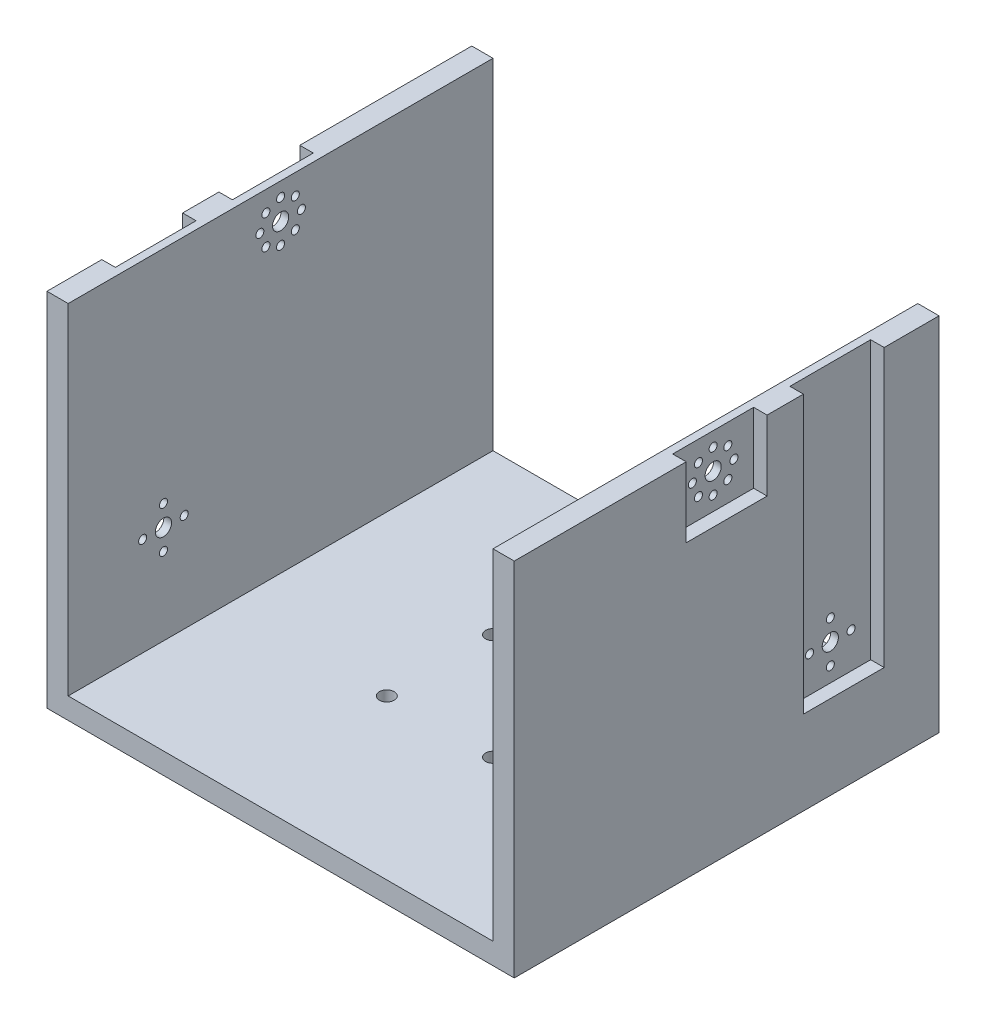
SolidWorks part; units mm, degrees
ref_plane "Front" through (0, 0, 0) normal (0, 0, 1) x (1, 0, 0)
ref_plane "Top" through (0, 0, 0) normal (0, 1, 0) x (1, 0, 0)
ref_plane "Right" through (0, 0, 0) normal (1, 0, 0) x (0, 0, -1)
sketch "Sketch2" plane through (0, 0, 0) normal (0, 1, 0) x (1, 0, 0)
  line L0 (0, 0) -> (0, -100) construction
  line L1 (-100, -100) -> (100, -100)
  line L2 (-100, -100) -> (-100, 100)
  line L3 (-100, 100) -> (100, 100)
  line L4 (100, -100) -> (100, 100)
  line L5 (0, 0) -> (-100, 0) construction
  point P0 (0, 0)
  dimension "D1" = 200
  dimension "D2" = 200
extrude "Boss-Extrude1" add sketch "Sketch2" along normal blind 10
sketch "Sketch3" plane through (0, 0, 0) normal (0, 1, 0) x (1, 0, 0)
  line L0 (-100, -100) -> (100, -100) construction
  line L1 (-100, 100) -> (-110, 100)
  line L2 (-100, 100) -> (-100, -100)
  line L3 (-100, -100) -> (-110, -100)
  line L4 (-110, 100) -> (-110, -100)
  line L5 (0, 0) -> (0, 100) construction
  line L6 (100, 100) -> (-100, 100) construction
  line L7 (110, 100) -> (110, -100)
  line L8 (100, -100) -> (110, -100)
  line L9 (100, 100) -> (100, -100)
  line L10 (100, 100) -> (110, 100)
  dimension "D1" = 10
extrude "Boss-Extrude2" add sketch "Sketch3" along normal blind 170
sketch "Sketch4" plane through (0, 10, 0) normal (0, 1, 0) x (1, 0, 0)
  point P4 (0, 0)
hole_wizard "M6 Clearance Hole1" positions "Sketch5" profile "Sketch6" hole size "M6" standard "ANSI Metric" end condition up to next
sketch "Sketch5" plane through (0, 10, 0) normal (0, 1, 0) x (1, 0, 0)
  line L0 (0, 0) -> (0, 25) construction
  line L1 (0, 25) -> (-25, 25) construction
  line L3 (0, 25) -> (25, 25) construction
  point P0 (-25, 25)
  point P13 (25, 25)
  point P14 (25, -25)
  point P15 (-25, -25)
  dimension "D1" = 25
  dimension "D2" = 4
sketch "Sketch6" plane through (-25, 10, -25) normal (1, 0, 0) x (0, 0, 1)
  line L0 (0, 0) -> (0, 10)
  line L1 (0, 10) -> (3.5, 10)
  line L2 (3.5, 10) -> (3.5, 0)
  line L5 (3.5, 0) -> (0, 0)
  line L11 (0, -6.35) -> (0, 107.95) construction
  dimension "Thru Hole Dia." = 7
  dimension "Thru Hole Depth" = 10
sketch "Sketch7" plane through (100, 0, 0) normal (-1, 0, 0) x (0, 0, 1)
  line L0 (-100, 170) -> (100, 170) construction
  line L1 (0, 153.49) -> (0, 163.269) construction
  line L2 (0, 153.49) -> (0, 163.269) construction
  circle A0 centre (0, 153.49) radius 3.81
  circle A1 centre (0, 163.269) radius 1.8987
  circle A2 centre (6.9148, 160.4048) radius 1.8987
  circle A3 centre (9.779, 153.49) radius 1.8987
  circle A4 centre (6.9148, 146.5752) radius 1.8987
  circle A5 centre (0, 143.711) radius 1.8987
  circle A6 centre (-6.9148, 146.5752) radius 1.8987
  circle A7 centre (-9.779, 153.49) radius 1.8987
  circle A8 centre (-6.9148, 160.4048) radius 1.8987
  point P7 (0, 170)
  dimension "D1" = 7.62
  dimension "D3" = 3.7973
  dimension "D2" = 16.51
  dimension "D6" = 9.779
  dimension "D5" = 8
extrude "Cut-Extrude1" cut sketch "Sketch7" against normal through all both and the other way through all
sketch "Sketch8" plane through (0, 170, 0) normal (0, 1, 0) x (1, 0, 0)
  line L1 (103.65, -19.05) -> (110, -19.05)
  line L2 (103.65, -19.05) -> (103.65, 19.05)
  line L3 (103.65, 19.05) -> (110, 19.05)
  line L4 (110, -19.05) -> (110, 19.05)
  line L5 (103.65, -19.05) -> (110, 19.05) construction
  line L6 (103.65, 19.05) -> (110, -19.05) construction
  line L9 (110, -100) -> (110, 100) construction
  line L10 (0, 0) -> (0, 100) construction
  line L11 (100, 100) -> (-100, 100) construction
  line L13 (-103.65, 19.05) -> (-110, -19.05) construction
  line L14 (-103.65, -19.05) -> (-110, 19.05) construction
  line L16 (-110, -19.05) -> (-110, 19.05)
  line L17 (-103.65, 19.05) -> (-110, 19.05)
  line L18 (-103.65, -19.05) -> (-103.65, 19.05)
  line L19 (-103.65, -19.05) -> (-110, -19.05)
  point P0 (106.825, 0)
  point P12 (110, 0)
  point P23 (-106.825, 0)
  dimension "D1" = 38.1
  dimension "D2" = 6.35
extrude "Cut-Extrude2" cut sketch "Sketch8" against normal blind 33.02
sketch "Sketch9" plane through (110, 0, 0) normal (1, 0, 0) x (0, 0, -1)
  line L0 (38.6402, 39.5213) -> (44.7362, 39.5213) construction
  line L2 (74.1602, 73.0593) -> (74.1602, 39.5113)
  line L3 (74.1602, 39.5113) -> (36.1402, 39.5113)
  line L4 (36.1402, 73.0593) -> (36.1402, 39.5113)
  line L5 (74.1602, 73.0593) -> (36.1402, 39.5113) construction
  line L6 (74.1602, 39.5113) -> (36.1402, 73.0593) construction
  line L7 (38.6402, 48.6653) -> (38.6402, 39.5213) construction
  line L13 (74.1602, 73.0593) -> (74.1602, 170)
  line L14 (19.05, 170) -> (100, 170) construction
  line L15 (74.1602, 170) -> (36.1402, 170)
  line L16 (36.1402, 170) -> (36.1402, 73.0593)
  point P0 (55.1502, 56.2853)
  point P10 (55.1502, 66.0643)
  point P11 (45.3712, 56.2853)
  point P13 (55.1502, 46.5063)
  point P15 (64.9292, 56.2853)
  dimension "D1" = 0.01
  dimension "D2" = 2.5
extrude "Cut-Extrude3" cut sketch "Sketch9" against normal blind 6.35
sketch "Sketch11" plane through (103.65, 0, 0) normal (1, 0, 0) x (0, 0, -1)
  circle A0 centre (55.1502, 56.2853) radius 3.81
  circle A1 centre (0, 153.49) radius 3.81 construction
extrude "Cut-Extrude4" cut sketch "Sketch11" against normal up to next
hole_wizard "#6 Clearance Hole1" positions "Sketch12" profile "Sketch13" hole size "#6" standard "ANSI Inch" end condition up to next
sketch "Sketch12" plane through (103.65, 0, 0) normal (1, 0, 0) x (0, 0, -1)
  point P0 (55.1502, 66.0643)
  point P3 (45.3712, 56.2853)
  point P6 (64.9292, 56.2853)
  point P10 (55.1502, 46.5063)
sketch "Sketch13" plane through (103.65, 66.0643, -55.1502) normal (0, 1, 0) x (0, 0, -1)
  line L0 (0, 0) -> (0, 3.65)
  line L1 (0, 3.65) -> (1.8986, 3.65)
  line L2 (1.8986, 3.65) -> (1.8986, 0)
  line L5 (1.8986, 0) -> (0, 0)
  line L11 (0, -6.35) -> (0, 107.95) construction
  dimension "Thru Hole Dia." = 3.7973
  dimension "Thru Hole Depth" = 3.65
ref_plane "Plane1" through (0, 0, 0) normal (-0.7071, 0, 0.7071) x (0.7071, 0, 0.7071)
ref_axis "Axis1" through (0, 0, 0) along (0, 1, 0)
pattern_circular "CirPattern1" count 2 over 360 about axis through (0, 0, 0) along (0, 1, 0) of "Cut-Extrude3", "Cut-Extrude4", "#6 Clearance Hole1"
sketch "Esquisse1" plane through (0, 10, 0) normal (0, 1, 0) x (1, 0, 0)
  circle A0 centre (53, 84.1347) radius 3.175
  circle A1 centre (53, -16.4015) radius 3.175
extrude "Enlèv. mat.-Extru.1" cut sketch "Esquisse1" against normal up to next
equation "\"Longueur\"= 200"
equation "\"D2@Sketch2\"=\"Longueur\""
equation "\"Largeur\"=200"
equation "\"D1@Sketch2\"=\"Largeur\""
